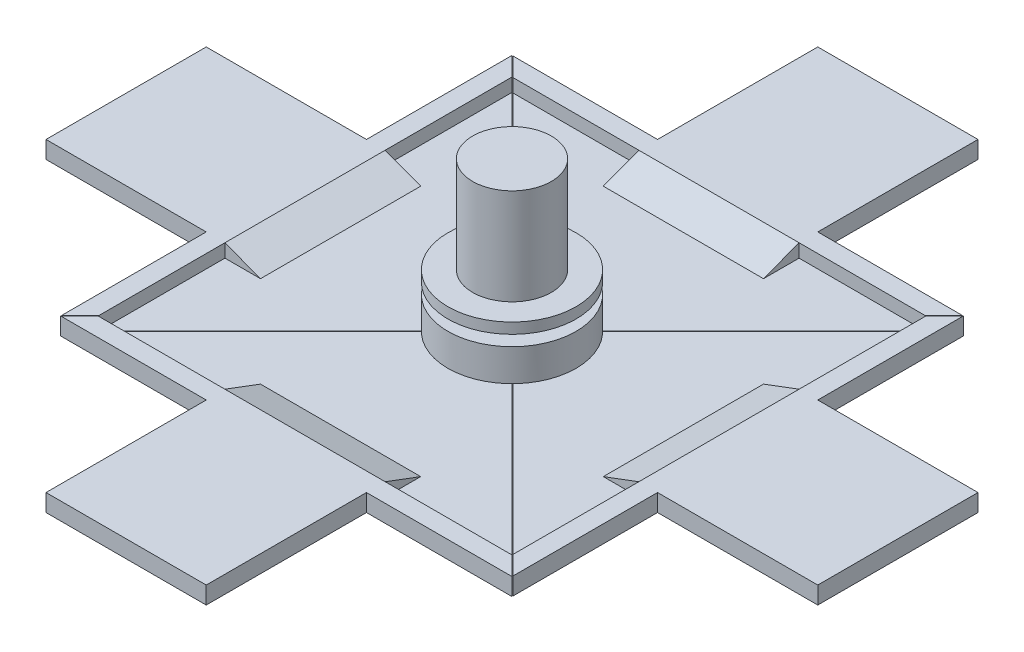
SolidWorks part; units mm, degrees
ref_plane "Front Plane" through (0, 0, 0) normal (0, 0, 1) x (1, 0, 0)
ref_plane "Top Plane" through (0, 0, 0) normal (0, 1, 0) x (1, 0, 0)
ref_plane "Right Plane" through (0, 0, 0) normal (1, 0, 0) x (0, 0, -1)
sketch "Field Layout" plane through (0, 0, 0) normal (0, 1, 0) x (1, 0, 0)
  line L0 (-984.25, -984.25) -> (984.25, -984.25)
  line L1 (-984.25, -984.25) -> (-984.25, 984.25)
  line L2 (-984.25, 984.25) -> (984.25, 984.25)
  line L3 (984.25, 984.25) -> (984.25, -984.25)
  line L4 (-984.25, -984.25) -> (984.25, 984.25) construction
  line L5 (984.25, -984.25) -> (0, 0)
  line L6 (-984.25, -984.25) -> (0, 0)
  line L7 (0, 0) -> (0, -1950.025) construction
  line L8 (-1073.15, 1073.15) -> (1073.15, 1073.15)
  line L9 (-1073.15, 1073.15) -> (-1073.15, -1073.15)
  line L10 (-1073.15, -1073.15) -> (1073.15, -1073.15)
  line L11 (1073.15, 1073.15) -> (1073.15, -1073.15)
  line L12 (-381, -1073.15) -> (381, -1073.15)
  line L13 (-381, -1073.15) -> (-381, -1835.15)
  line L14 (-381, -1835.15) -> (381, -1835.15)
  line L15 (381, -1073.15) -> (381, -1835.15)
  line L16 (-1073.15, 381) -> (-1835.15, 381)
  line L17 (-1073.15, 381) -> (-1073.15, -381)
  line L18 (-1073.15, -381) -> (-1835.15, -381)
  line L19 (-1835.15, 381) -> (-1835.15, -381)
  line L20 (381, 1073.15) -> (381, 1835.15)
  line L21 (381, 1073.15) -> (-381, 1073.15)
  line L22 (-381, 1073.15) -> (-381, 1835.15)
  line L23 (381, 1835.15) -> (-381, 1835.15)
  line L24 (1073.15, -381) -> (1835.15, -381)
  line L25 (1073.15, -381) -> (1073.15, 381)
  line L26 (1073.15, 381) -> (1835.15, 381)
  line L27 (1835.15, -381) -> (1835.15, 381)
  line L28 (381, -1835.15) -> (-381, -1073.15) construction
  line L29 (-152.4, -1746.25) -> (152.4, -1162.05) construction
  line L30 (-152.4, -1746.25) -> (152.4, -1746.25)
  line L31 (-152.4, -1746.25) -> (-152.4, -1162.05)
  line L32 (-152.4, -1162.05) -> (152.4, -1162.05)
  line L33 (152.4, -1746.25) -> (152.4, -1162.05)
  line L34 (-984.25, 381) -> (-815.1118, 381)
  line L35 (-381, -984.25) -> (381, -984.25)
  line L36 (-381, -984.25) -> (-381, -815.1118)
  line L37 (-381, -815.1118) -> (381, -815.1118)
  line L38 (381, -984.25) -> (381, -815.1118)
  line L39 (-815.1118, 381) -> (-815.1118, -381)
  line L40 (-984.25, -381) -> (-815.1118, -381)
  line L41 (-1746.25, 152.4) -> (-1162.05, 152.4)
  line L42 (-1746.25, 152.4) -> (-1746.25, -152.4)
  line L43 (-1746.25, -152.4) -> (-1162.05, -152.4)
  line L44 (-1162.05, 152.4) -> (-1162.05, -152.4)
  line L45 (381, 984.25) -> (381, 815.1118)
  line L46 (381, 815.1118) -> (-381, 815.1118)
  line L47 (-381, 984.25) -> (-381, 815.1118)
  line L48 (152.4, 1746.25) -> (152.4, 1162.05)
  line L49 (152.4, 1746.25) -> (-152.4, 1746.25)
  line L50 (-152.4, 1746.25) -> (-152.4, 1162.05)
  line L51 (152.4, 1162.05) -> (-152.4, 1162.05)
  line L52 (984.25, -381) -> (815.1118, -381)
  line L53 (815.1118, -381) -> (815.1118, 381)
  line L54 (984.25, 381) -> (815.1118, 381)
  line L55 (1746.25, -152.4) -> (1162.05, -152.4)
  line L56 (1746.25, -152.4) -> (1746.25, 152.4)
  line L57 (1746.25, 152.4) -> (1162.05, 152.4)
  line L58 (1162.05, -152.4) -> (1162.05, 152.4)
  circle A0 centre (0, 0) radius 304.8
  point P2 (0, 0)
  point P16 (0, -1454.15)
  point P32 (0, 0)
  point P66 (0, 0)
  dimension "D3" = 609.6
  dimension "D1" = 1968.5
  dimension "D2" = 1968.5
  dimension "D4" = 88.9
  dimension "D5" = 88.9
  dimension "D6" = 762
  dimension "D8" = 584.2
  dimension "D9" = 304.8
  dimension "D7" = 4
  dimension "D10" = 4
extrude "Plywood Base" add sketch "Field Layout" against normal blind 19.05 contours L16 L19 L18 L9 L41 L44 L43 L42 | L44 L41 L42 L43 | L11 L8 L9 L10 L2 L3 L0 L1 | L1 L40 L39 L34 | A0 L5 L3 L52 L53 L54 L2 L45 L46 L47 L1 L34 L39 L40 L6 | A0 L6 L0 L36 L37 L38 L5 | L6 A0 L5 | L5 A0 L6 | L0 L38 L37 L36 | L30 L33 L32 L31 | L15 L10 L13 L14 L33 L30 L31 L32 | L3 L54 L53 L52 | L24 L27 L26 L11 L55 L58 L57 L56 | L58 L55 L56 L57 | L2 L47 L46 L45 | L20 L23 L22 L8 L48 L51 L50 L49 | L51 L48 L49 L50 region at (0, 0, 660.2665) region at (-956.4112, 0, 682.625) region at (0, 0, 899.6809) region at (-899.6809, 0, 0) region at (0, 0, -60.9814) region at (0, 0, 182.9443) region at (899.6809, 0, 0) region at (0, 0, -899.6809) region at (-727.075, 0, -1042.7967) region at (-370.2237, 0, -1454.15) region at (-1083.9263, 0, 0) region at (1454.15, 0, -370.2237) region at (0, 0, 1083.9263) region at (0, 0, 1454.15) region at (-1454.15, 0, 0) region at (0, 0, -1454.15) region at (1454.15, 0, 0)
extrude "Raised Base" add sketch "Field Layout<3>" along normal blind 63.5 contours L16 L19 L18 L9 L41 L44 L43 L42 | L44 L41 L42 L43 | L11 L8 L9 L10 L2 L3 L0 L1 | L15 L10 L13 L14 L33 L30 L31 L32 | L30 L33 L32 L31 | L58 L55 L56 L57 | L24 L27 L26 L11 L55 L58 L57 L56 | L51 L48 L49 L50 | L20 L23 L22 L8 L48 L51 L50 L49 region at (-727.075, 0, -1042.7967) region at (-370.2237, 0, -1454.15) region at (-1083.9263, 0, 0) region at (1454.15, 0, -370.2237) region at (0, 0, 1083.9263) region at (0, 0, 1454.15) region at (-1454.15, 0, 0) region at (0, 0, -1454.15) region at (1454.15, 0, 0)
sketch "Field Layout<3>" plane through (0, 0, 0) normal (0, 1, 0) x (1, 0, 0) same geometry as "Field Layout"
extrude "Ramp Extrude" add sketch "Field Layout<4>" along normal blind 63.5 contours L0 L38 L37 L36 region at (0, 0, 899.6809)
sketch "Field Layout<4>" plane through (0, 0, 0) normal (0, 1, 0) x (1, 0, 0) same geometry as "Field Layout"
sketch "Sketch3" plane through (381, 0, 0) normal (1, 0, 0) x (0, 0, -1)
  line L4 (-984.25, 63.5) -> (-815.1118, 0)
  line L8 (-984.25, 0) -> (-815.1118, 0)
  line L9 (-815.1118, 0) -> (-815.1118, 63.5)
  line L10 (-815.1118, 63.5) -> (-984.25, 63.5)
  line L11 (-984.25, 63.5) -> (-984.25, 0)
  line L12 (-984.25, 0) -> (-815.1118, 0)
  line L13 (-815.1118, 0) -> (-815.1118, 63.5)
  line L14 (-815.1118, 63.5) -> (-984.25, 63.5)
  line L15 (-984.25, 63.5) -> (-984.25, 0)
  line M6 (-815.1118, 0) -> (-815.1118, 63.5)
  line M7 (-815.1118, 63.5) -> (-984.25, 63.5)
  dimension "D1" = 0
extrude "Cut ramp slope" cut sketch "Sketch3" against normal up to next contours L4 M7 M6 region at (381, 42.3333, 871.4912)
pattern_circular "Copy Ramp Slope" count 4 over 360 about axis through (0, -19.05, 0) along (0, -1, 0) of "Ramp Extrude", "Cut ramp slope"
sketch "Sketch5" plane through (0, 0, 0) normal (0, 1, 0) x (1, 0, 0)
  circle A0 centre (0, 0) radius 304.8
  dimension "D1" = 609.6
extrude "Boss-Extrude1" add sketch "Sketch5" along normal blind 254 separate body
sketch "Sketch4" plane through (0, 0, 0) normal (0, 1, 0) x (1, 0, 0)
  line L0 (-984.25, -984.25) -> (984.25, 984.25)
  line L1 (-984.25, 984.25) -> (984.25, -984.25)
  line L3 (984.25, 984.25) -> (1073.15, 1073.15)
  line L4 (-984.25, -984.25) -> (-1073.15, -1073.15)
  line L5 (984.25, -984.25) -> (1073.15, -1073.15)
  line L6 (-984.25, 984.25) -> (-1073.15, 1073.15)
extrude "Cut-Extrude-Thin1" cut sketch "Sketch4" against normal through all both and the other way through all thin thin type one direction wall 2.54
sketch "Sketch6" plane through (0, 254, 0) normal (0, 1, 0) x (1, 0, 0)
  circle A0 centre (0, 0) radius 187.2268
extrude "Boss-Extrude2" add sketch "Sketch6" along normal blind 457.2
sketch "Sketch7" plane through (0, 0, 0) normal (0, 0, 1) x (1, 0, 0)
  line L0 (304.8, 203.2) -> (228.4457, 203.2)
  line L1 (304.8, 0) -> (304.8, 254) construction
  line L2 (228.4457, 203.2) -> (228.4457, 152.4)
  line L3 (228.4457, 152.4) -> (304.8, 152.4)
  line L4 (304.8, 152.4) -> (304.8, 203.2)
  line L5 (304.8, 254) -> (-304.8, 254) construction
  line L6 (0, 0) -> (0, 385.2882) construction
  dimension "D1" = 50.8
  dimension "D2" = 152.4
revolve "Cut-Revolve1" cut sketch "Sketch7" angle 360 about L6
